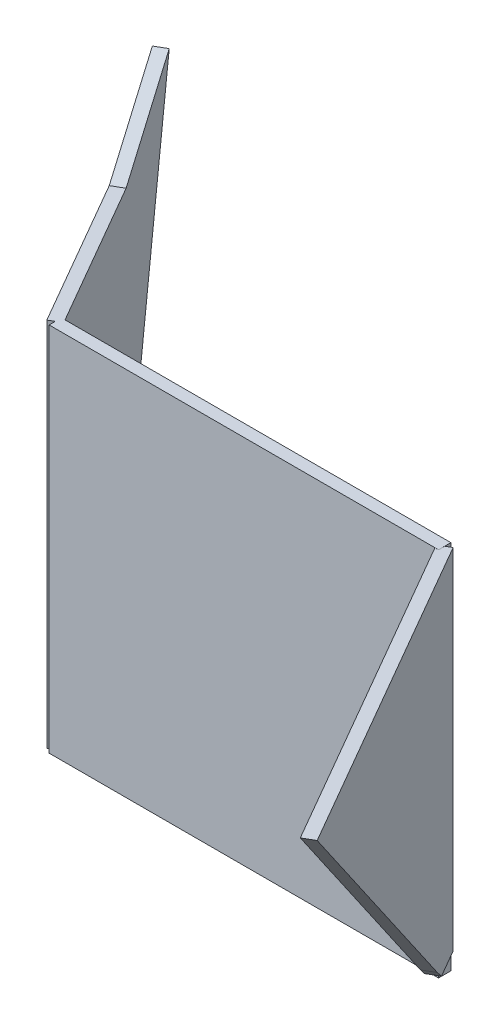
SolidWorks part; units mm, degrees
material "AISI 1020"
ref_plane "Plano frontal" through (0, 0, 0) normal (0, 0, 1) x (1, 0, 0)
ref_plane "Plano superior" through (0, 0, 0) normal (0, 1, 0) x (1, 0, 0)
ref_plane "Plano direito" through (0, 0, 0) normal (1, 0, 0) x (0, 0, -1)
sketch "Esboço1" plane through (0, 0, 0) normal (0, 0, 1) x (1, 0, 0)
  line L1 (-31.5, -30) -> (31.5, -30)
  line L2 (-31.5, -30) -> (-31.5, 30)
  line L3 (-31.5, 30) -> (31.5, 30)
  line L4 (31.5, -30) -> (31.5, 30)
  line L5 (-31.5, -30) -> (31.5, 30) construction
  line L6 (-31.5, 30) -> (31.5, -30) construction
  point P0 (0, 0)
  dimension "D1" = 63
  dimension "D2" = 60
extrude "Ressalto-extrusão1" add sketch "Esboço1" along normal mid plane 2
ref_axis "Eixo1" through (31.5, 30, 0) along (0, -1, 0)
ref_plane "Plano1" through (23.625, 0, -13.6399) normal (-0.866, 0, 0.5) x (0, -1, 0)
sketch "Esboço2" plane through (23.625, 0, -13.6399) normal (-0.866, 0, 0.5) x (0, -1, 0)
  line L0 (30.0044, 15.75) -> (30.0044, 30.6454) construction
  line L1 (-29.9956, 15.75) -> (30.0044, 15.75)
  line L2 (-29.9956, 15.75) -> (-29.9956, 75.8492)
  line L5 (-30, 15.75) -> (30, 15.75) construction
  line L6 (24.7744, 22.7386) -> (-29.9956, 75.8492)
  line L7 (24.7744, 15.75) -> (24.7744, 30.6454) construction
  line L8 (24.7744, 15.75) -> (24.7744, 22.7386) construction
  line L9 (24.7744, 20.9186) -> (26.5344, 20.9186) construction
  line L10 (26.5344, 20.9186) -> (24.7744, 22.7386)
  line L11 (26.5344, 20.9186) -> (26.5344, 15.75)
  dimension "D1" = 5.23
  dimension "D2" = 60.0992
  dimension "D3" = 44.119
  dimension "D4" = 1.82
  dimension "D5" = 1.76
extrude "Ressalto-extrusão2" add sketch "Esboço2" along normal mid plane 2 contours L1 L8 L6 L2 region at (41.588, 9.6319, 17.473)
ref_axis "Eixo2" through (-31.5, 58.2761, 0) along (0, -1, 0)
ref_plane "Plano2" through (-23.625, 0, 13.6399) normal (0.866, 0, -0.5) x (0, -1, 0)
sketch "Esboço3" plane through (-23.625, 0, 13.6399) normal (0.866, 0, -0.5) x (0, -1, 0)
  line L1 (30, 15.75) -> (-30, 15.75)
  line L5 (-58.2761, 15.75) -> (51.7239, 15.75) construction
  line L6 (-30, 14.884) -> (-30, 16.616) construction
  line L12 (30, 15.75) -> (17.6436, 43.3264)
  line L13 (17.6436, 43.3264) -> (-36.5522, 62.3759)
  line L14 (-36.5522, 62.3759) -> (-30, 43.3264)
  line L15 (-30, 43.3264) -> (-30, 15.75)
  dimension "D1" = 60
extrude "Ressalto-extrusão3" add sketch "Esboço3" along normal mid plane 2
